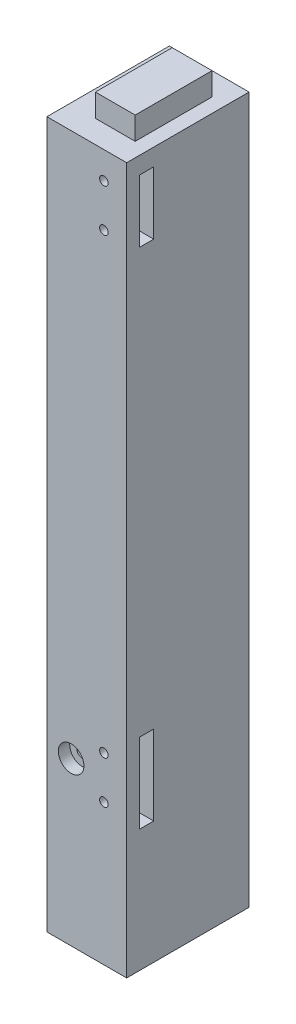
SolidWorks part; units mm, degrees
ref_plane "Front Plane" through (0, 0, 0) normal (0, 0, 1) x (1, 0, 0)
ref_plane "Top Plane" through (0, 0, 0) normal (0, 1, 0) x (1, 0, 0)
ref_plane "Right Plane" through (0, 0, 0) normal (1, 0, 0) x (0, 0, -1)
sketch "Sketch1" plane through (0, 0, 0) normal (0, 0, 1) x (1, 0, 0)
  line L1 (44.45, 393.7) -> (-44.45, 393.7)
  line L2 (44.45, 393.7) -> (44.45, -393.7)
  line L3 (44.45, -393.7) -> (-44.45, -393.7)
  line L4 (-44.45, 393.7) -> (-44.45, -393.7)
  line L5 (44.45, 393.7) -> (-44.45, -393.7) construction
  line L6 (44.45, -393.7) -> (-44.45, 393.7) construction
  point P0 (0, 0)
  dimension "D1" = 787.4
  dimension "D2" = 88.9
extrude "Boss-Extrude1" add sketch "Sketch1" along normal blind 136.525
sketch "Sketch2" plane through (0, 393.7, 0) normal (0, 1, 0) x (1, 0, 0)
  line L0 (-44.45, -136.525) -> (-44.45, 0) construction
  line L1 (-15.875, -25.4) -> (28.575, -25.4)
  line L2 (-15.875, -25.4) -> (-15.875, -111.125)
  line L3 (-15.875, -111.125) -> (28.575, -111.125)
  line L4 (28.575, -25.4) -> (28.575, -111.125)
  line L5 (-15.875, -25.4) -> (28.575, -111.125) construction
  line L6 (-15.875, -111.125) -> (28.575, -25.4) construction
  line L7 (44.45, 0) -> (-44.45, 0) construction
  point P0 (6.35, -68.2625)
  dimension "D1" = 85.725
  dimension "D2" = 28.575
  dimension "D3" = 44.45
  dimension "D4" = 25.4
extrude "Boss-Extrude2" add sketch "Sketch2" along normal blind 25.4 contours L2 L3 L4 L1
sketch "Sketch4" plane through (44.45, 0, 0) normal (1, 0, 0) x (0, 0, -1)
  line L0 (-136.525, 393.7) -> (0, 393.7) construction
  line L1 (-122.2375, -168.275) -> (-106.3625, -168.275)
  line L2 (-122.2375, -168.275) -> (-122.2375, -257.175)
  line L3 (-122.2375, -257.175) -> (-106.3625, -257.175)
  line L4 (-106.3625, -168.275) -> (-106.3625, -257.175)
  line L5 (-122.2375, -168.275) -> (-106.3625, -257.175) construction
  line L6 (-122.2375, -257.175) -> (-106.3625, -168.275) construction
  line L7 (-122.2375, 374.65) -> (-106.3625, 374.65)
  line L8 (-122.2375, 374.65) -> (-122.2375, 304.8)
  line L9 (-122.2375, 304.8) -> (-106.3625, 304.8)
  line L10 (-106.3625, 374.65) -> (-106.3625, 304.8)
  line L11 (-122.2375, 374.65) -> (-106.3625, 304.8) construction
  line L12 (-122.2375, 304.8) -> (-106.3625, 374.65) construction
  line L14 (-136.525, -393.7) -> (-136.525, 393.7) construction
  line L15 (-136.525, -393.7) -> (0, -393.7) construction
  point P0 (-114.3, -212.725)
  point P5 (-114.3, 339.725)
  point P17 (-68.2625, -393.7)
  dimension "D1" = 69.85
  dimension "D2" = 19.05
  dimension "D3" = 15.875
  dimension "D4" = 14.2875
  dimension "D5" = 88.9
  dimension "D6" = 136.525
  dimension "D7" = 15.875
extrude "Cut-Extrude1" cut sketch "Sketch4" against normal blind 50.8
sketch "Sketch5" plane through (0, 0, 0) normal (0, 0, -1) x (-1, 0, 0)
  line L0 (44.45, -393.7) -> (-44.45, -393.7) construction
  line L1 (30.1625, -171.45) -> (4.7625, -171.45)
  line L2 (30.1625, -171.45) -> (30.1625, -254)
  line L3 (30.1625, -254) -> (4.7625, -254)
  line L4 (4.7625, -171.45) -> (4.7625, -254)
  line L5 (30.1625, -171.45) -> (4.7625, -254) construction
  line L6 (30.1625, -254) -> (4.7625, -171.45) construction
  line L7 (44.45, 393.7) -> (44.45, -393.7) construction
  point P0 (17.4625, -212.725)
  dimension "D1" = 25.4
  dimension "D2" = 82.55
  dimension "D3" = 139.7
  dimension "D4" = 14.2875
extrude "Cut-Extrude2" cut sketch "Sketch5" against normal blind 50.8
sketch "Sketch6" plane through (0, 0, 136.525) normal (0, 0, 1) x (1, 0, 0)
  line L0 (-4.7625, -171.45) -> (-4.7625, -254) construction
  line L1 (-4.7625, -254) -> (-30.1625, -254) construction
  line L2 (-30.1625, -254) -> (-30.1625, -171.45) construction
  line L3 (-30.1625, -171.45) -> (-4.7625, -171.45) construction
  line L4 (44.45, -168.275) -> (44.45, -257.175) construction
  line L5 (44.45, -257.175) -> (-6.35, -257.175) construction
  line L6 (-6.35, -257.175) -> (-6.35, -168.275) construction
  line L7 (-6.35, -168.275) -> (44.45, -168.275) construction
  line L8 (44.45, 374.65) -> (44.45, 304.8) construction
  line L9 (44.45, 304.8) -> (-6.35, 304.8) construction
  line L10 (-6.35, 304.8) -> (-6.35, 374.65) construction
  line L11 (-6.35, 374.65) -> (44.45, 374.65) construction
  line L12 (-4.7625, -171.45) -> (-4.7625, -254)
  line L13 (-4.7625, -254) -> (-30.1625, -254)
  line L14 (-30.1625, -254) -> (-30.1625, -171.45)
  line L15 (-30.1625, -171.45) -> (-4.7625, -171.45)
  line L16 (44.45, -168.275) -> (44.45, -257.175)
  line L17 (44.45, -257.175) -> (-6.35, -257.175)
  line L18 (-6.35, -257.175) -> (-6.35, -168.275)
  line L19 (-6.35, -168.275) -> (44.45, -168.275)
  line L20 (44.45, 374.65) -> (44.45, 304.8)
  line L21 (44.45, 304.8) -> (-6.35, 304.8)
  line L22 (-6.35, 304.8) -> (-6.35, 374.65)
  line L23 (-6.35, 374.65) -> (44.45, 374.65)
  line L24 (-30.1625, -171.45) -> (-4.7625, -254) construction
  line L25 (19.05, 374.65) -> (19.05, 304.8) construction
  line L26 (19.05, -168.275) -> (19.05, -257.175) construction
  circle A0 centre (-17.4625, -212.725) radius 6.35
  circle A1 centre (-17.4625, -212.725) radius 14.2875
  circle A2 centre (19.05, 363.5375) radius 4.7625
  circle A3 centre (19.05, 315.9125) radius 4.7625
  circle A4 centre (19.05, -236.5375) radius 4.7625
  circle A5 centre (19.05, -188.9125) radius 4.7625
  point P21 (19.05, 339.725)
  point P28 (19.05, -212.725)
  dimension "D1" = 12.7
  dimension "D2" = 28.575
  dimension "D3" = 9.525
  dimension "D4" = 23.8125
  dimension "D7" = 9.525
  dimension "D8" = 23.8125
  dimension "D9" = 23.8125
  dimension "D5" = 23.8125
  dimension "D6" = 25.4
  dimension "D10" = 25.4
extrude "Cut-Extrude3" cut sketch "Sketch6" against normal blind 12.7 contours A1
sketch "Sketch7" plane through (0, 0, 123.825) normal (0, 0, 1) x (1, 0, 0)
  circle A0 centre (-17.4625, -212.725) radius 6.35
  dimension "D1" = 12.7
extrude "Cut-Extrude4" cut sketch "Sketch7" against normal through all
extrude "Cut-Extrude5" cut sketch "Sketch6<4>" against normal blind 44.45 contours A4 | A3 | A5 | A2 region at (19.05, 315.9125, 136.525) region at (19.05, -236.5375, 136.525)
sketch "Sketch6<4>" plane through (0, 0, 136.525) normal (0, 0, 1) x (1, 0, 0) same geometry as "Sketch6"
